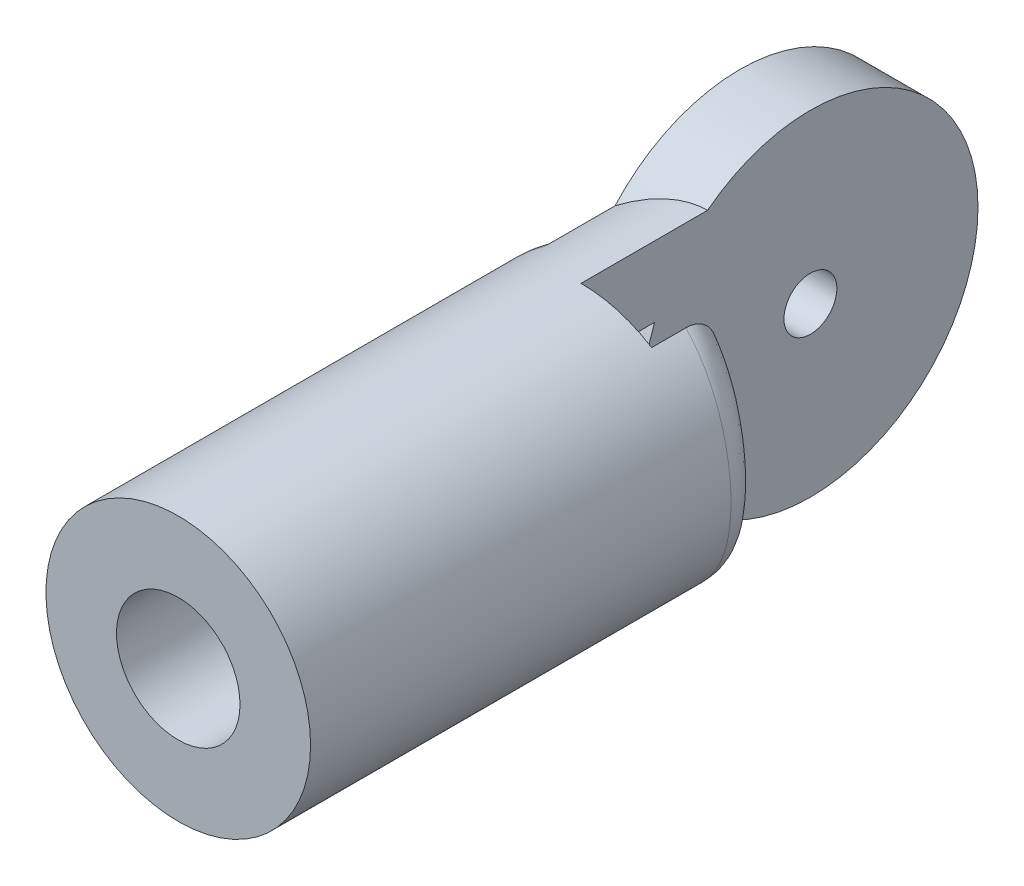
SolidWorks part; units mm, degrees
ref_plane "Спереди" through (0, 0, 0) normal (0, 0, 1) x (1, 0, 0)
ref_plane "Сверху" through (0, 0, 0) normal (0, 1, 0) x (1, 0, 0)
ref_plane "Справа" through (0, 0, 0) normal (1, 0, 0) x (0, 0, -1)
sketch "Sketch1" plane through (0, 0, 0) normal (0, 0, 1) x (1, 0, 0)
  circle A0 centre (0, 0) radius 3.5
  circle A1 centre (0, 0) radius 7.5
  dimension "D1" = 7
  dimension "D2" = 4
extrude "Boss-Extrude1" add sketch "Sketch1" along normal blind 30
sketch "Sketch2" plane through (0, 0, 0) normal (1, 0, 0) x (0, 0, -1)
  circle A0 centre (5.831, 0) radius 9.5
  dimension "D1" = 19
extrude "Boss-Extrude2" add sketch "Sketch2" along normal mid plane 8
sketch "Sketch4" plane through (-4, 0, 0) normal (-1, 0, 0) x (0, 0, 1)
  circle A0 centre (-5.831, 0) radius 1.5
  dimension "D1" = 3
extrude "Cut-Extrude1" cut sketch "Sketch4" against normal mid plane 34
sketch "Sketch5" plane through (4, 0, 0) normal (1, 0, 0) x (0, 0, -1)
  circle A0 centre (5.831, 0) radius 10
extrude "Cut-Extrude2" cut sketch "Sketch5" along normal blind 31
sketch "Sketch6" plane through (-4, 0, 0) normal (-1, 0, 0) x (0, 0, 1)
  circle A0 centre (-5.831, 0) radius 10
extrude "Cut-Extrude3" cut sketch "Sketch6" along normal blind 25
fillet "Fillet3" radius 2 2 edges at (7.4994, 0.0941, 4.1686) (-7.4994, -0.0941, 4.1686)
sketch "Sketch7" plane through (4, 0, 0) normal (1, 0, 0) x (0, 0, -1)
  line L1 (18.831, 13) -> (-7.169, 13)
  line L2 (18.831, 13) -> (18.831, -13)
  line L3 (18.831, -13) -> (-7.169, -13)
  line L4 (-7.169, 13) -> (-7.169, -13)
  line L5 (18.831, 13) -> (-7.169, -13) construction
  line L6 (18.831, -13) -> (-7.169, 13) construction
  point P0 (5.831, 0)
  dimension "D1" = 26
extrude "Cut-Extrude4" cut sketch "Sketch7" against normal blind 4
